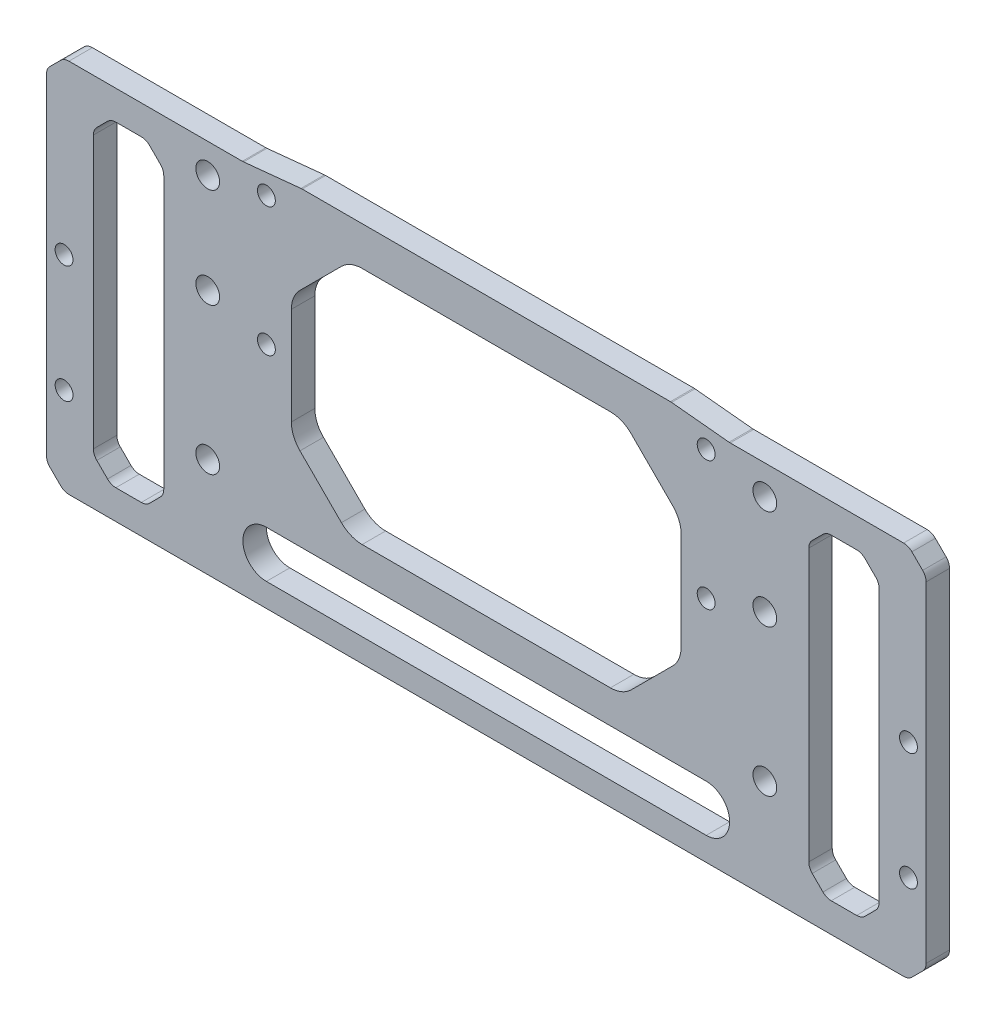
SolidWorks part; units mm, degrees
material "Thornel Mat VMA"
ref_plane "前视基准面" through (0, 0, 0) normal (0, 0, 1) x (1, 0, 0)
ref_plane "上视基准面" through (0, 0, 0) normal (0, 1, 0) x (1, 0, 0)
ref_plane "右视基准面" through (0, 0, 0) normal (1, 0, 0) x (0, 0, -1)
other "Configuration Table"
sketch "草图1" plane through (0, 0, 0) normal (0, 0, 1) x (1, 0, 0)
  line L0 (-47.5, 4) -> (47.5, 4) construction
  line L1 (-47.5, -21) -> (47.5, -21) construction
  line L2 (-47.5, -21) -> (-47.5, 21) construction
  line L3 (-47.5, 21) -> (47.5, 21) construction
  line L4 (47.5, -21) -> (47.5, 21) construction
  line L5 (-47.5, -21) -> (47.5, 21) construction
  line L6 (-47.5, 21) -> (47.5, -21) construction
  line L7 (0, 0) -> (50000, 0) construction
  line L8 (-52.5, -26) -> (52.5, -26)
  line L9 (-52.5, -26) -> (-52.5, 26)
  line L10 (-52.5, 26) -> (52.5, 26)
  line L11 (52.5, -26) -> (52.5, 26)
  line L12 (-52.5, -26) -> (52.5, 26) construction
  line L13 (-52.5, 26) -> (52.5, -26) construction
  line L14 (-39, -22.5) -> (-17, -22.5) construction
  line L15 (-39, -22.5) -> (-39, 22.5) construction
  line L16 (-39, 22.5) -> (-17, 22.5) construction
  line L17 (-17, -22.5) -> (-17, 22.5) construction
  line L18 (-39, -22.5) -> (-17, 22.5) construction
  line L19 (-39, 22.5) -> (-17, -22.5) construction
  line L20 (0, 0) -> (0, -50000) construction
  line L22 (-37.5, 1) -> (37.5, 1) construction
  line L23 (-37.5, 1) -> (-37.5, 23) construction
  line L24 (-37.5, 23) -> (37.5, 23) construction
  line L25 (37.5, 1) -> (37.5, 23) construction
  line L26 (-37.5, 1) -> (37.5, 23) construction
  line L27 (-37.5, 23) -> (37.5, 1) construction
  line L28 (-41.5, 26) -> (41.5, 26)
  line L29 (-41.5, 26) -> (-41.5, 27)
  line L30 (-41.5, 27) -> (41.5, 27)
  line L31 (41.5, 26) -> (41.5, 27)
  circle A0 centre (-47.5, 4) radius 2.025
  circle A1 centre (-47.5, 21) radius 2.025
  circle A2 centre (-47.5, -21) radius 2.025
  circle A3 centre (47.5, 21) radius 2.025
  circle A4 centre (47.5, 4) radius 2.025
  circle A5 centre (47.5, -21) radius 2.025
  circle A6 centre (-39, 22.5) radius 1.525 construction
  circle A7 centre (-17, 22.5) radius 1.525 construction
  circle A8 centre (-39, -22.5) radius 1.525 construction
  circle A9 centre (-17, -22.5) radius 1.525 construction
  circle A10 centre (-37.5, 23) radius 1.525
  circle A11 centre (-37.5, 1) radius 1.525
  circle A12 centre (37.5, 23) radius 1.525
  circle A13 centre (37.5, 1) radius 1.525
  point P0 (0, 0)
  point P14 (0, 0)
  point P19 (-28, 0)
  point P32 (0, 12)
  dimension "D1" = 4.05
  dimension "D2" = 25
  dimension "D3" = 17
  dimension "D9" = 3.05
  dimension "D4" = 95
  dimension "D5" = 5
  dimension "D6" = 5
  dimension "D7" = 22
  dimension "D8" = 45
  dimension "D10" = 28
  dimension "D11" = 75
  dimension "D12" = 22
  dimension "D13" = 1
  dimension "D14" = 4
  dimension "D15" = 4
extrude "凸台-拉伸3" add sketch "草图1" along normal blind 4 contours L10 L31 L30 L29 A13 A12 A11 A10 | L8 L11 L10 L9 A9 A8 A7 A6 A5 A4 A3 A2 A1 A0 region at (0, -0.0848, 0) region at (0, 26.5, 0)
sketch "草图3" plane through (0, 0, 4) normal (0, 0, 1) x (1, 0, 0)
  line L0 (52.5, -26) -> (52.5, 26) construction
  line L1 (-52.5, 26) -> (-55, 26)
  line L2 (-52.5, 26) -> (-52.5, -38)
  line L3 (-52.5, -38) -> (-55, -38)
  line L4 (-55, 26) -> (-55, -38)
  line L5 (-52.5, -38) -> (52.5, -38)
  line L6 (-52.5, -38) -> (-52.5, -26)
  line L7 (-52.5, -26) -> (52.5, -26)
  line L8 (52.5, -38) -> (52.5, -26)
  line L9 (-52.5, -26) -> (52.5, -26) construction
  line L10 (41.5, 26) -> (52.5, 26) construction
  line L11 (52.5, -38) -> (55, -38)
  line L12 (52.5, -38) -> (52.5, 26)
  line L13 (52.5, 26) -> (55, 26)
  line L14 (55, -38) -> (55, 26)
  line M13 (-52.5, 26) -> (-52.5, -26)
  line M14 (-52.5, -26) -> (52.5, -26)
  line M15 (52.5, -26) -> (52.5, 26)
  dimension "D1" = 2.5
  dimension "D2" = 12
extrude "凸台-拉伸4" add sketch "草图3" against normal up to surface (4 mm away) contours L5 L8 L2 M14 | L1 L4 L3 L2 M13 | L11 L14 L13 L8 M15 region at (-53.75, -6, 4) region at (0, -32, 4) region at (53.75, -6, 4) up to face at (0, 13.25, 0)
sketch "草图4" plane through (0, 0, 4) normal (0, 0, 1) x (1, 0, 0)
  circle A0 centre (-37.5, 23) radius 3
  dimension "D1" = 6
sketch "草图5" plane through (0, 0, 0) normal (0, 0, -1) x (-1, 0, 0)
  circle A0 centre (37.5, 23) radius 3
  circle A1 centre (37.5, 1) radius 3
  circle A2 centre (37.5, 23) radius 3 construction
sketch "草图6" plane through (0, 0, 0) normal (0, 0, -1) x (-1, 0, 0)
  line L0 (37.5, 23) -> (33.2378, 20.3859) construction
  line L1 (-33.2378, -20.3859) -> (33.2378, -20.3859)
  line L2 (-33.2378, -20.3859) -> (-33.2378, 20.3859)
  line L3 (-33.2378, 20.3859) -> (33.2378, 20.3859)
  line L4 (33.2378, -20.3859) -> (33.2378, 20.3859)
  line L5 (-33.2378, -20.3859) -> (33.2378, 20.3859) construction
  line L6 (-33.2378, 20.3859) -> (33.2378, -20.3859) construction
  circle A0 centre (37.5, 23) radius 5
  point P0 (0, 0)
  dimension "D1" = 10
extrude "切除-拉伸1" cut sketch "草图6" against normal blind 4 contours L1 L4 L3 L2 region at (0, 0, 0)
chamfer "倒角1" distance 10 angle 45 4 edges at (-33.2378, -20.3859, 2) (-33.2378, 20.3859, 2) (33.2378, 20.3859, 2) (33.2378, -20.3859, 2)
fillet "圆角2" radius 5 8 edges at (33.2378, 10.3859, 2) (23.2378, 20.3859, 2) (-23.2378, 20.3859, 2) (-33.2378, 10.3859, 2) (-23.2378, -20.3859, 2) (23.2378, -20.3859, 2) (33.2378, -10.3859, 2) (-33.2378, -10.3859, 2)
sketch "草图7" plane through (0, 0, 4) normal (0, 0, 1) x (1, 0, 0)
  line L0 (-72, -3) -> (-72, -23) construction
  line L1 (-55, 26) -> (-75, 26)
  line L2 (-55, 26) -> (-55, -38)
  line L3 (-55, -38) -> (-75, -38)
  line L4 (-75, 26) -> (-75, -38)
  line L5 (55, 26) -> (75, 26)
  line L6 (55, 26) -> (55, -38)
  line L7 (55, -38) -> (75, -38)
  line L8 (75, 26) -> (75, -38)
  line L9 (-72, -23) -> (-72, -38) construction
  line L10 (0, 0) -> (0, -50000) construction
  circle A0 centre (-72, -3) radius 1.525
  circle A1 centre (-72, -23) radius 1.525
  circle A2 centre (72, -23) radius 1.525
  circle A3 centre (72, -3) radius 1.525
  dimension "D5" = 3.05
  dimension "D1" = 20
  dimension "D2" = 20
  dimension "D3" = 15
  dimension "D4" = 3
extrude "凸台-拉伸5" add sketch "草图7" against normal up to surface (4 mm away) up to face at (0, 0, 0)
sketch "草图8" plane through (0, 0, 4) normal (0, 0, 1) x (1, 0, 0)
  line L0 (-75, 26) -> (-41.5, 26) construction
  line L1 (-67, 21) -> (-55, 21)
  line L2 (-67, 21) -> (-67, -33)
  line L3 (-67, -33) -> (-55, -33)
  line L4 (-55, 21) -> (-55, -33)
  line L5 (-75, -38) -> (75, -38) construction
  line L6 (0, 0) -> (0, -50000) construction
  line L7 (67, -33) -> (55, -33)
  line L8 (55, 21) -> (55, -33)
  line L9 (67, 21) -> (55, 21)
  line L10 (67, 21) -> (67, -33)
  circle A0 centre (-72, -3) radius 1.525 construction
  circle A1 centre (-47.5, 21) radius 2.025 construction
  dimension "D1" = 5
  dimension "D2" = 5
  dimension "D3" = 5
  dimension "D4" = 7.5
extrude "切除-拉伸2" cut sketch "草图8" against normal blind 10
sketch "草图9" plane through (0, 0, 4) normal (0, 0, 1) x (1, 0, 0)
  line L0 (41.5, 26) -> (31.5, 27)
  line L1 (-41.5, 27) -> (41.5, 27) construction
  line L2 (31.5, 27) -> (41.5, 27)
  line L3 (41.5, 27) -> (41.5, 26)
  line L4 (0, 0) -> (0, 12.0137) construction
  line L5 (-41.5, 27) -> (-41.5, 26)
  line L6 (-31.5, 27) -> (-41.5, 27)
  line L7 (-41.5, 26) -> (-31.5, 27)
  line L8 (-37.5, -30) -> (37.5, -30) construction
  line L9 (-37.5, -26) -> (37.5, -26)
  line L10 (-37.5, -34) -> (37.5, -34)
  line L11 (-75, -38) -> (75, -38) construction
  arc A0 (-37.5, -26) -> (-37.5, -34) centre (-37.5, -30) ccw
  arc A1 (37.5, -34) -> (37.5, -26) centre (37.5, -30) ccw
  point P15 (0, -30)
  dimension "D3" = 4
  dimension "D1" = 10
  dimension "D2" = 4
  dimension "D4" = 75
extrude "切除-拉伸3" cut sketch "草图9" against normal blind 10
chamfer "倒角2" distance 3 angle 45 12 edges at (75, -38, 2) (75, 26, 2) (-75, 26, 2) (-75, -38, 2) (-67, -33, 2) (-55, -33, 2) (-67, 21, 2) (-55, 21, 2) (55, -33, 2) (67, -33, 2) (55, 21, 2) (67, 21, 2)
fillet "圆角3" radius 2 28 edges at (75, 23, 2) (72, 26, 2) (41.5, 26, 2) (31.5, 27, 2) (-31.5, 27, 2) (-41.5, 26, 2) (-72, 26, 2) (-75, 23, 2) (-75, -35, 2) (-72, -38, 2) (75, -35, 2) (55, 18, 2) (58, 21, 2) (64, 21, 2) (67, 18, 2) (67, -30, 2) (64, -33, 2) (58, -33, 2) (55, -30, 2) (-55, -30, 2) (-58, -33, 2) (-64, -33, 2) (-67, -30, 2) (-67, 18, 2) (-64, 21, 2) (-58, 21, 2) (-55, 18, 2) (72, -38, 2)
